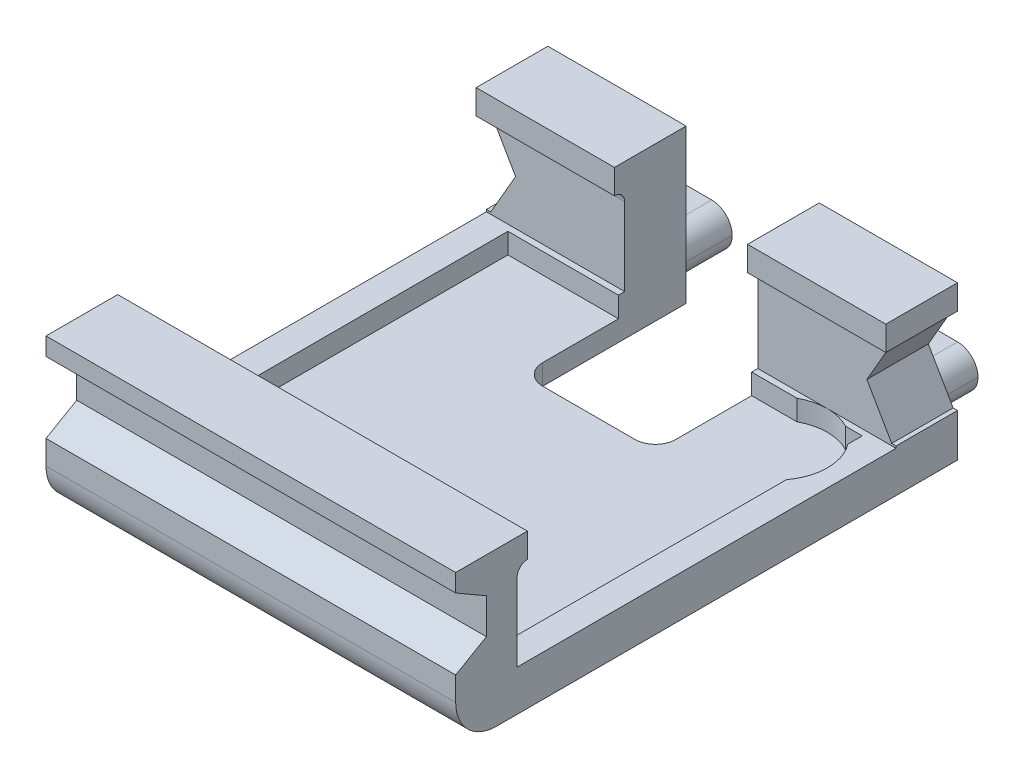
SolidWorks part; units mm, degrees
ref_plane "Front Plane" through (0, 0, 0) normal (0, 0, 1) x (1, 0, 0)
ref_plane "Top Plane" through (0, 0, 0) normal (0, 1, 0) x (1, 0, 0)
ref_plane "Right Plane" through (0, 0, 0) normal (1, 0, 0) x (0, 0, -1)
sketch "Sketch1" plane through (0, 0, 0) normal (0, 1, 0) x (1, 0, 0)
  line L0 (0, 11.5) -> (0, -11.5) construction
  line L1 (10, 11.5) -> (-10, 11.5)
  line L2 (10, 11.5) -> (10, -11.5)
  line L3 (10, -11.5) -> (-10, -11.5)
  line L4 (-10, 11.5) -> (-10, -11.5)
  line L5 (10, 11.5) -> (-10, -11.5) construction
  line L6 (10, -11.5) -> (-10, 11.5) construction
  line L21 (-3.25, 3.5) -> (3.25, 3.5)
  line L29 (-3.25, 3.5) -> (-3.25, 11.5)
  line L30 (-3.25, 11.5) -> (3.25, 11.5)
  line L31 (3.25, 3.5) -> (3.25, 11.5)
  line L32 (-3.25, 3.5) -> (3.25, 11.5) construction
  line L33 (-3.25, 11.5) -> (3.25, 3.5) construction
  line L41 (-6, 14.5) -> (-6, 11.5) construction
  line L42 (-4, 11.5) -> (-8, 11.5)
  line L43 (-4, 11.5) -> (-4, 14.5)
  line L44 (-4, 14.5) -> (-8, 14.5)
  line L45 (-8, 11.5) -> (-8, 14.5)
  line L46 (4, 11.5) -> (8, 11.5)
  line L47 (8, 11.5) -> (8, 14.5)
  line L48 (4, 14.5) -> (8, 14.5)
  line L49 (4, 11.5) -> (4, 14.5)
  point P0 (0, 0)
  point P14 (0, 7.5)
  dimension "D1" = 20
  dimension "D2" = 23
  dimension "D3" = 4
  dimension "D6" = 6.5
  dimension "D7" = 8
  dimension "D8" = 12
  dimension "D9" = 3
extrude "Boss-Extrude1" add sketch "Sketch1" along normal blind 2 contours L4 | L1 L4 L3 L2 | L2 | L31 L21 L29 L1 | L43 L1 | L1 region at (0, 0, 0.9559) region at (6, 0, -13) region at (-6, 0, -13)
fillet "Fillet1" radius 1 10 edges at (-3.25, 1, -3.5) (3.25, 1, -3.5) (-8, 0, -13) (-8, 2, -13) (4, 0, -13) (4, 2, -13) (8, 0, -13) (8, 2, -13) (-4, 0, -13) (-4, 2, -13)
sketch "Sketch4" plane through (0, 2, 0) normal (0, 1, 0) x (1, 0, 0)
  line L0 (0, 5.3573) -> (0, -4.2859) construction
  line L2 (-8.65, 8.2) -> (8.65, 8.2)
  line L3 (-8.65, 8.2) -> (-8.65, -9.5)
  line L4 (-8.65, -9.5) -> (8.65, -9.5)
  line L5 (8.65, 8.2) -> (8.65, -9.5)
  line L6 (-8.65, 8.2) -> (8.65, -9.5) construction
  line L7 (-8.65, -9.5) -> (8.65, 8.2) construction
  line L11 (10, -11.5) -> (-10, -11.5) construction
  point P1 (0, -0.65)
  dimension "D1" = 17.3
  dimension "D2" = 2
  dimension "D3" = 17.7
extrude "Cut-Extrude3" cut sketch "Sketch4" against normal blind 1
sketch "Sketch5" plane through (10, 0, 0) normal (1, 0, 0) x (0, 0, -1)
  line L0 (8.2, 1) -> (-9.5, 1) construction
  line L1 (8.2, 1) -> (-9.5, 1)
  line L2 (11.5, 2) -> (-11.5, 2) construction
  line L3 (-11.5, 2) -> (-10, 2)
  line L4 (-11.5, 2) -> (-11.5, 6.3)
  line L5 (-11.5, 6.3) -> (-10, 6.3)
  line L6 (-10, 2) -> (-10, 6.3)
  line L7 (11.5, 2) -> (8.5, 2)
  line L8 (11.5, 2) -> (11.5, 6.3)
  line L9 (11.5, 6.3) -> (8.5, 6.3)
  line L10 (8.5, 2) -> (8.5, 6.3)
  line L11 (-11.5, 6.3) -> (-9.5, 6.3)
  line L12 (-11.5, 6.3) -> (-11.5, 7.5)
  line L13 (-11.5, 7.5) -> (-9.5, 7.5)
  line L14 (-9.5, 6.3) -> (-9.5, 7.5)
  line L15 (11.5, 6.3) -> (8, 6.3)
  line L16 (11.5, 6.3) -> (11.5, 7.5)
  line L17 (11.5, 7.5) -> (8, 7.5)
  line L18 (8, 6.3) -> (8, 7.5)
  line L19 (-11.5, 2) -> (-11.5, 0) construction
  line L20 (11.5, 2) -> (11.5, 0) construction
  point P22 (0, 0)
  dimension "D1" = 1.5
  dimension "D2" = 5.3
  dimension "D3" = 18.5
  dimension "D4" = 1.2
  dimension "D5" = 0.5
  dimension "D6" = 0.5
extrude "Boss-Extrude3" add sketch "Sketch5" against normal up to surface (20 mm away) contours L6 L5 L4 | L11 L14 L13 L12 L5 | L18 L15 L9 L16 L17 | L10 L7 L8 L9 region at (10, 4.15, 10.75) region at (10, 6.9, 10.5) region at (10, 4.15, -10) region at (10, 6.9, -9.75) up to face at (-10, 1, 0)
sketch "Sketch7" plane through (0, 7.5, 0) normal (0, 1, 0) x (1, 0, 0)
  line L1 (-3.25, 11.5) -> (3.25, 11.5)
  line L2 (-3.25, 11.5) -> (-3.25, 8)
  line L3 (-3.25, 8) -> (3.25, 8)
  line L4 (3.25, 11.5) -> (3.25, 8)
  line L5 (-10, 8) -> (10, 8) construction
  line L11 (0, 5.6258) -> (0, -4.3103) construction
  line L16 (3.25, 4.5) -> (3.25, 8.2) construction
  line L17 (-10, 8) -> (10, 8) construction
  point P5 (3.25, 8)
extrude "Cut-Extrude5" cut sketch "Sketch7" against normal up to next
sketch "Sketch8" plane through (0, 0, -11.5) normal (0, 0, -1) x (-1, 0, 0)
  line L0 (-3.25, 7.5) -> (-10, 7.5) construction
  line L1 (-8.5751, 4.2) -> (-9.7876, 6.3)
  line L2 (-9.7876, 6.3) -> (-12.2124, 6.3)
  line L3 (-12.2124, 6.3) -> (-13.4249, 4.2)
  line L4 (-13.4249, 4.2) -> (-12.2124, 2.1)
  line L5 (-12.2124, 2.1) -> (-9.7876, 2.1)
  line L6 (-9.7876, 2.1) -> (-8.5751, 4.2)
  line L7 (0, 12.0608) -> (0, -4.099) construction
  line L8 (12.2124, 2.1) -> (9.7876, 2.1)
  line L9 (13.4249, 4.2) -> (12.2124, 2.1)
  line L10 (12.2124, 6.3) -> (13.4249, 4.2)
  line L11 (9.7876, 6.3) -> (12.2124, 6.3)
  line L12 (8.5751, 4.2) -> (9.7876, 6.3)
  line L13 (9.7876, 2.1) -> (8.5751, 4.2)
  circle A0 centre (-11, 4.2) radius 2.1 construction
  dimension "D1" = 3.3
  dimension "D2" = 22
  dimension "D3" = 4.2
extrude "Cut-Extrude6" cut sketch "Sketch8" against normal blind 3.5
fillet "Fillet3" radius 0.5 3 edges at (6.5188, 6.3, -8.5) (-6.5188, 6.3, -8.5) (0, 6.3, 10)
sketch "Sketch9" plane through (10, 0, 0) normal (1, 0, 0) x (0, 0, -1)
  line L0 (-11.5, 7.5) -> (-11.5, 0) construction
  line L1 (-11.5, 4.034) -> (-11.5, 5.766)
  line L2 (-11.5, 5.766) -> (-13, 6.6321)
  line L3 (-13, 6.6321) -> (-14.5, 5.766)
  line L4 (-14.5, 5.766) -> (-14.5, 4.034)
  line L5 (-14.5, 4.034) -> (-13, 3.1679)
  line L6 (-13, 3.1679) -> (-11.5, 4.034)
  line L7 (-11.5, 7.5) -> (-9.5, 7.5) construction
  line L8 (-13, 6.6321) -> (-13, 7.5)
  line L9 (-13, 7.5) -> (-11.5, 7.5)
  line L10 (-13, 3.1679) -> (-13, 0)
  line L11 (-13, 0) -> (-11.5, 0)
  circle A0 centre (-13, 4.9) radius 1.5 construction
  line M11 (-11.5, 7.5) -> (-11.5, 0)
  dimension "D1" = 3
  dimension "D2" = 2.6
extrude "Boss-Extrude4" add sketch "Sketch9" against normal up to surface (20 mm away) contours L9 L8 L2 M11 | L10 L11 L6 M11 region at (10, 1.8092, 12.2199) region at (10, 6.8255, 12.1668) up to face at (-10, 3.5404, 2.2104)
sketch "Sketch10" plane through (0, 2, 0) normal (0, 1, 0) x (1, 0, 0)
  line L2 (10, 8.5) -> (3.25, 8.5) construction
  line L3 (8.65, -9.5) -> (8.65, 8.2) construction
  circle A0 centre (6.65, 6) radius 2.5
  point P6 (9.15, 6)
  dimension "D2" = 5
  dimension "D1" = 0.5
extrude "Cut-Extrude7" cut sketch "Sketch10" against normal up to surface (1 mm away) up to face at (0, 1, -2.9386)
fillet "Fillet4" radius 2 1 edges at (0, 0, 13)
